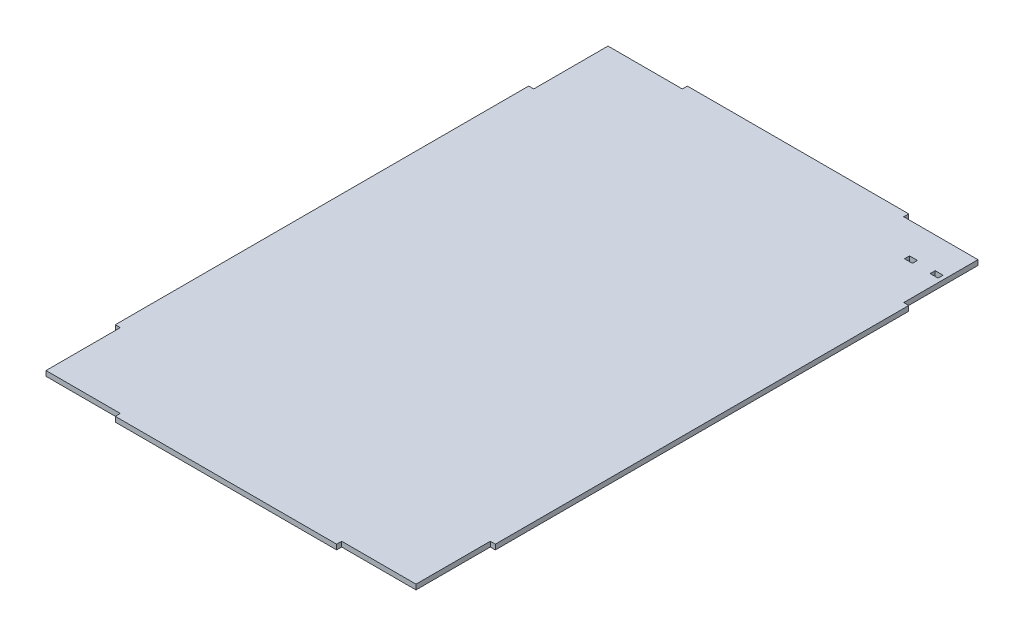
SolidWorks part; units mm, degrees
ref_plane "Front Plane" through (0, 0, 0) normal (0, 0, 1) x (1, 0, 0)
ref_plane "Top Plane" through (0, 0, 0) normal (0, 1, 0) x (1, 0, 0)
ref_plane "Right Plane" through (0, 0, 0) normal (1, 0, 0) x (0, 0, -1)
sketch "Sketch1" plane through (0, 0, 0) normal (0, 1, 0) x (1, 0, 0)
  line L7 (-239.5, -360.5) -> (239.5, -360.5)
  line L8 (-239.5, -360.5) -> (-239.5, 360.5)
  line L9 (-239.5, 360.5) -> (239.5, 360.5)
  line L10 (239.5, -360.5) -> (239.5, 360.5)
  point P0 (0, 0)
  point P3 (239.5, 0)
  point P6 (0, 0)
  point P11 (0, -360.5)
  dimension "D1" = 721
  dimension "D2" = 479
extrude "Boss-Extrude1" add sketch "Sketch1" along normal mid plane 6.35
sketch "Sketch2" plane through (0, 3.175, 0) normal (0, 1, 0) x (1, 0, 0)
  line L0 (-239.5, 360.5) -> (-239.5, 260.5)
  line L1 (-239.5, 360.5) -> (-239.5, -360.5) construction
  line L2 (-239.5, 260.5) -> (-233.15, 260.5)
  line L3 (-233.15, 260.5) -> (-233.15, 354.15)
  line L4 (-233.15, 354.15) -> (-139.5, 354.15)
  line L5 (-139.5, 354.15) -> (-139.5, 360.5)
  line L6 (239.5, 360.5) -> (-239.5, 360.5) construction
  line L7 (-139.5, 360.5) -> (-239.5, 360.5)
  line L8 (239.5, 360.5) -> (139.5, 360.5)
  line L9 (139.5, 360.5) -> (139.5, 354.15)
  line L10 (139.5, 354.15) -> (233.15, 354.15)
  line L11 (233.15, 354.15) -> (233.15, 260.5)
  line L12 (233.15, 260.5) -> (239.5, 260.5)
  line L13 (239.5, -360.5) -> (239.5, 360.5) construction
  line L14 (239.5, 260.5) -> (239.5, 360.5)
  line L15 (239.5, -360.5) -> (239.5, -260.5)
  line L16 (239.5, -260.5) -> (233.15, -260.5)
  line L17 (233.15, -260.5) -> (233.15, -354.15)
  line L18 (233.15, -354.15) -> (139.5, -354.15)
  line L19 (139.5, -354.15) -> (139.5, -360.5)
  line L20 (-239.5, -360.5) -> (239.5, -360.5) construction
  line L21 (139.5, -360.5) -> (239.5, -360.5)
  line L22 (-239.5, -360.5) -> (-139.5, -360.5)
  line L23 (-139.5, -360.5) -> (-139.5, -354.15)
  line L24 (-139.5, -354.15) -> (-233.15, -354.15)
  line L25 (-233.15, -354.15) -> (-233.15, -260.5)
  line L26 (-233.15, -260.5) -> (-239.5, -260.5)
  line L27 (-239.5, -260.5) -> (-239.5, -360.5)
  dimension "D1" = 100
  dimension "D2" = 6.35
extrude "Cut-Extrude1" cut sketch "Sketch2" against normal through all
sketch "Sketch3" plane through (0, -3.175, 0) normal (0, -1, 0) x (1, 0, 0)
  line L0 (233.15, -354.15) -> (233.15, -260.5) construction
  line L1 (139.5, -354.15) -> (233.15, -354.15) construction
  line L8 (185.85, -308.8) -> (195.85, -308.8)
  line L9 (185.85, -308.8) -> (185.85, -315.15)
  line L10 (185.85, -315.15) -> (195.85, -315.15)
  line L11 (195.85, -308.8) -> (195.85, -315.15)
  line L12 (228.15, -308.8) -> (228.15, -315.15)
  line L13 (218.15, -308.8) -> (228.15, -308.8)
  line L14 (218.15, -308.8) -> (218.15, -315.15)
  line L15 (218.15, -315.15) -> (228.15, -315.15)
  dimension "D1" = 10
  dimension "D2" = 6.35
  dimension "D3" = 5
  dimension "D4" = 42.3
  dimension "D5" = 39
extrude "Cut-Extrude2" cut sketch "Sketch3" against normal through all
